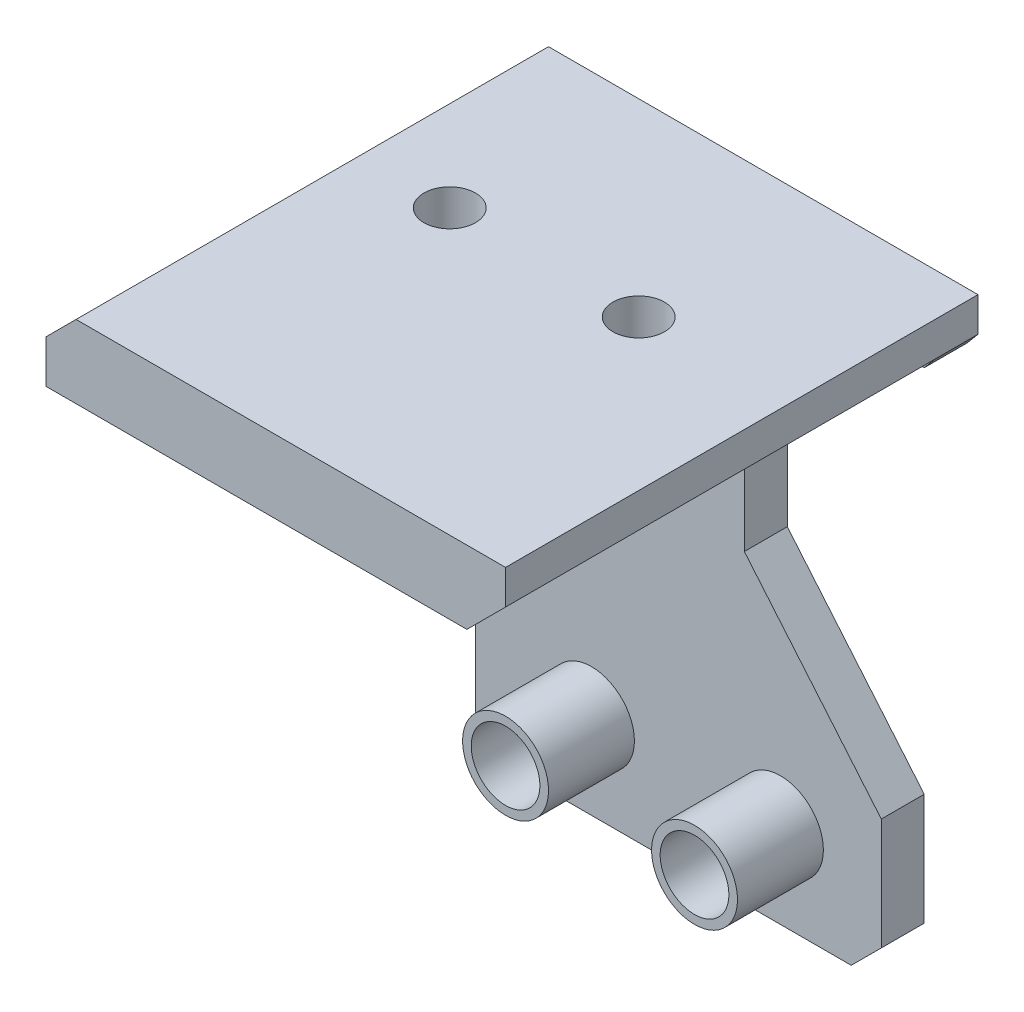
SolidWorks part; units mm, degrees
material "ABS"
ref_plane "Front Plane" through (0, 0, 0) normal (0, 0, 1) x (1, 0, 0)
ref_plane "Top Plane" through (0, 0, 0) normal (0, 1, 0) x (1, 0, 0)
ref_plane "Right Plane" through (0, 0, 0) normal (1, 0, 0) x (0, 0, -1)
sketch "Sketch1" plane through (0, 0, 0) normal (0, 0, 1) x (1, 0, 0)
  line L21 (53.5, -0.5) -> (53.5, 3.5)
  line L22 (52.2414, -2) -> (53.5, -0.5)
  line L23 (47.2414, -2) -> (52.2414, -2)
  line L24 (47.2414, -63) -> (43.7414, -66.5)
  line L25 (53.5, 3.5) -> (3.5, 3.5)
  line L26 (31.2985, -21) -> (47.2414, -2)
  line L27 (31.2985, -31) -> (31.2985, -21)
  line L28 (47.2414, -50) -> (31.2985, -31)
  line L30 (43.7414, -66.5) -> (47.2414, -63)
  line L31 (47.2414, -63) -> (47.2414, -50)
  line L32 (3.5, 3.5) -> (0, 0)
  line L33 (0, -63) -> (3.5, -66.5)
  line L34 (3.5, -66.5) -> (43.7414, -66.5)
  line L38 (0, 0) -> (0, -63)
  dimension "D1" = 63
  dimension "D2" = 50
  dimension "D3" = 53.5
  dimension "D4" = 5
  dimension "D5" = 70
  dimension "D6" = 10
  dimension "D7" = 48
  dimension "D8" = 13
  dimension "D9" = 4
  dimension "D10" = 1.5
  dimension "D11" = 3.5
  dimension "D12" = 130
  dimension "D13" = 130
  dimension "D14" = 135
  dimension "D15" = 135
  dimension "D16" = 19
extrude "Boss-Extrude1" add sketch "Sketch1" along normal blind 5 contours L38 | L32 L38 L33 L34 L24 L31 L28 L27 L26 L23 L22 L21 L25 region at (21.1694, -31.9385, 0)
sketch "Sketch2" plane through (0, 0, 5) normal (0, 0, 1) x (1, 0, 0)
  line L0 (0, -5) -> (0, 0)
  line L2 (0, 0) -> (3.5, 3.5)
  line L3 (3.5, 3.5) -> (53.5, 3.5)
  line L4 (3.5, 3.5) -> (0, 0) construction
  line L5 (53.5, 3.5) -> (53.5, -0.5)
  line L6 (53.5, -0.5) -> (49, -5)
  line L7 (49, -5) -> (0, -5)
  line L8 (53.5, 3.5) -> (3.5, 3.5) construction
  line L9 (53.5, -0.5) -> (53.5, 3.5) construction
  dimension "D1" = 5
extrude "Boss-Extrude2" add sketch "Sketch2" along normal blind 50
sketch "Sketch3" plane through (0, -5, 0) normal (0, -1, 0) x (1, 0, 0)
  line L0 (3.5, 0) -> (43.7414, 0) construction
  line L2 (0, 55) -> (0, 5) construction
  circle A0 centre (36, 22) radius 3
  circle A1 centre (14, 22) radius 3
  circle A2 centre (36, 22) radius 5
  circle A3 centre (14, 22) radius 5
  dimension "D1" = 6
  dimension "D2" = 22
  dimension "D3" = 14
  dimension "D4" = 22
  dimension "D5" = 10
extrude "Cut-Extrude1" cut sketch "Sketch3" against normal through all and the other way through all contours A0 | A1
sketch "Sketch4" plane through (0, 0, 5) normal (0, 0, 1) x (1, 0, 0)
  line L0 (0, -5) -> (0, -63) construction
  line L2 (53.5, 3.5) -> (3.5, 3.5) construction
  circle A0 centre (13.5, -56.5) radius 4
  circle A1 centre (35.5, -56.5) radius 4
  circle A2 centre (13.5, -56.5) radius 5
  circle A3 centre (35.5, -56.5) radius 5
  dimension "D1" = 8
  dimension "D2" = 10
  dimension "D3" = 22
  dimension "D5" = 13.5
  dimension "D4" = 60
extrude "Boss-Extrude3" add sketch "Sketch4" along normal blind 10
extrude "Cut-Extrude2" cut sketch "Sketch3<3>" against normal blind 4 contours A2 A0 | A3 A1 region at (31.1414, -5, 22) region at (9.1414, -5, 22)
sketch "Sketch3<3>" plane through (0, -5, 0) normal (0, -1, 0) x (1, 0, 0) same geometry as "Sketch3"
sketch "Esquisse1" plane through (0, 0, 5) normal (0, 0, 1) x (1, 0, 0)
  circle A0 centre (35.5, -56.5) radius 4
  circle A1 centre (13.5, -56.5) radius 4
  dimension "D1" = 8
extrude "Enlèv. mat.-Extru.1" cut sketch "Esquisse1" against normal through all
